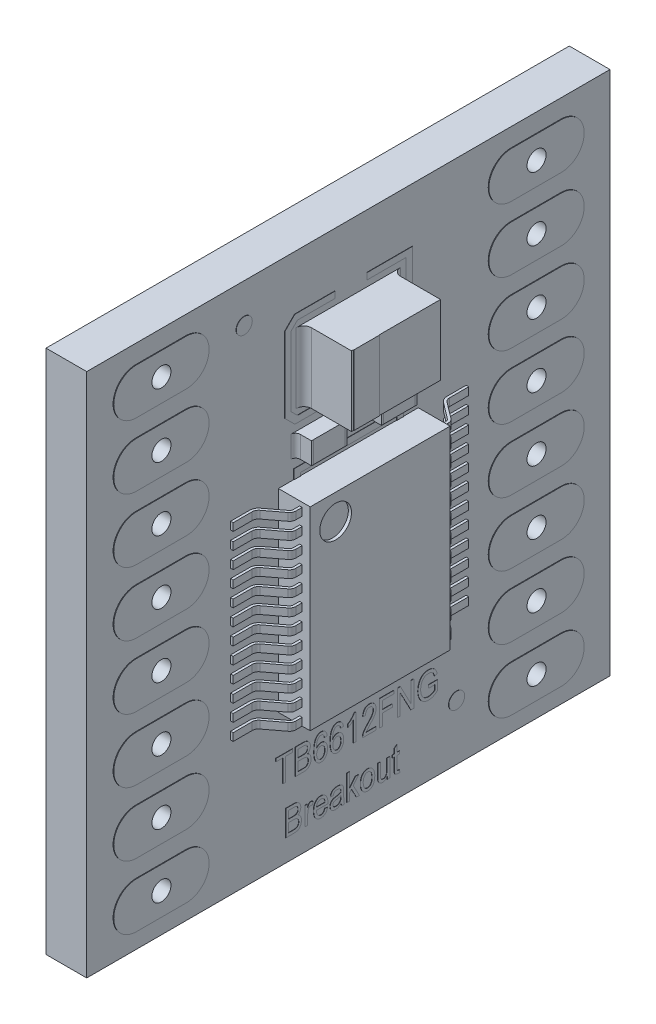
SolidWorks part; units mm, degrees
ref_plane "Front Plane" through (0, 0, 0) normal (0, 0, 1) x (1, 0, 0)
ref_plane "Top Plane" through (0, 0, 0) normal (0, 1, 0) x (1, 0, 0)
ref_plane "Right Plane" through (0, 0, 0) normal (1, 0, 0) x (0, 0, -1)
sketch "Sketch1" plane through (0, 0, 0) normal (1, 0, 0) x (0, 0, -1)
  line L1 (-10.4521, 10.4902) -> (10.4521, 10.4902)
  line L2 (-10.4521, 10.4902) -> (-10.4521, -10.4902)
  line L3 (-10.4521, -10.4902) -> (10.4521, -10.4902)
  line L4 (10.4521, 10.4902) -> (10.4521, -10.4902)
  line L5 (-10.4521, 10.4902) -> (10.4521, -10.4902) construction
  line L6 (-10.4521, -10.4902) -> (10.4521, 10.4902) construction
  point P0 (0, 0)
  dimension "D1" = 20.9804
  dimension "D2" = 20.9042
extrude "Boss-Extrude1" add sketch "Sketch1" along normal blind 1.6256
sketch "Sketch2" plane through (1.6256, 0, 0) normal (1, 0, 0) x (0, 0, -1)
  line L0 (-10.4521, -10.4902) -> (10.4521, -10.4902) construction
  line L1 (-2.794, 2.6162) -> (2.794, 2.6162)
  line L2 (-2.794, 2.6162) -> (-2.794, -5.1308)
  line L3 (-2.794, -5.1308) -> (2.794, -5.1308)
  line L4 (2.794, 2.6162) -> (2.794, -5.1308)
  line L5 (-2.794, 2.6162) -> (2.794, -5.1308) construction
  line L6 (-2.794, -5.1308) -> (2.794, 2.6162) construction
  point P0 (0, 0)
  dimension "D1" = 5.588
  dimension "D2" = 7.747
  dimension "D3" = 5.3594
extrude "Boss-Extrude2" add sketch "Sketch2" along normal blind 1.27
sketch "Sketch7" plane through (2.8956, 0, 0) normal (1, 0, 0) x (0, 0, -1)
  line L0 (-2.794, 2.6162) -> (-2.794, -5.1308) construction
  line L1 (2.794, 2.6162) -> (-2.794, 2.6162) construction
  circle A0 centre (-1.778, 1.6002) radius 0.635
  dimension "D1" = 1.27
  dimension "D2" = 1.016
  dimension "D3" = 1.016
extrude "Cut-Extrude2" cut sketch "Sketch7" against normal blind 0.127
sketch "Sketch4" plane through (1.6256, 0, 0) normal (1, 0, 0) x (0, 0, -1)
  line L0 (-7.493, 8.8392) -> (0, 8.8392) construction
  line L1 (0, 8.8392) -> (7.493, 8.8392) construction
  line L2 (0, 0) -> (0, 8.8392) construction
  line L3 (10.4521, 10.4902) -> (-10.4521, 10.4902) construction
  circle A0 centre (-7.493, 8.8392) radius 0.381
  circle A1 centre (7.493, 8.8392) radius 0.381
  dimension "D2" = 0.762
  dimension "D1" = 14.986
  dimension "D3" = 1.27
extrude "Cut-Extrude1" cut sketch "Sketch4" against normal through all
sketch "Sketch5" plane through (1.6256, 0, 0) normal (1, 0, 0) x (0, 0, -1)
  line L0 (-8.4836, 8.8392) -> (-6.5024, 8.8392) construction
  line L1 (-8.4836, 9.7536) -> (-6.5024, 9.7536)
  line L2 (-8.4836, 7.9248) -> (-6.5024, 7.9248)
  line L3 (6.5024, 8.8392) -> (8.4836, 8.8392) construction
  line L4 (6.5024, 9.7536) -> (8.4836, 9.7536)
  line L5 (6.5024, 7.9248) -> (8.4836, 7.9248)
  arc A0 (-8.4836, 9.7536) -> (-8.4836, 7.9248) centre (-8.4836, 8.8392) ccw
  arc A1 (-6.5024, 7.9248) -> (-6.5024, 9.7536) centre (-6.5024, 8.8392) ccw
  arc A2 (6.5024, 9.7536) -> (6.5024, 7.9248) centre (6.5024, 8.8392) ccw
  arc A3 (8.4836, 7.9248) -> (8.4836, 9.7536) centre (8.4836, 8.8392) ccw
  circle A6 centre (7.493, 8.8392) radius 0.381 construction
  circle A7 centre (-7.493, 8.8392) radius 0.381 construction
  circle A8 centre (7.493, 8.8392) radius 0.381
  circle A9 centre (-7.493, 8.8392) radius 0.381
  point P3 (-7.493, 8.8392)
  point P8 (7.493, 8.8392)
  point P18 (7.493, 8.8392)
  dimension "D2" = 3.81
  dimension "D1" = 1.8288
extrude "Boss-Extrude3" add sketch "Sketch5" along normal blind 0.0254
sketch "Sketch6" plane through (0, 0, 0) normal (-1, 0, 0) x (0, 0, 1)
  line L0 (-6.5024, 7.9248) -> (-8.4836, 7.9248) construction
  line L1 (-8.4836, 9.7536) -> (-6.5024, 9.7536) construction
  line L2 (8.4836, 7.9248) -> (6.5024, 7.9248) construction
  line L3 (6.5024, 9.7536) -> (8.4836, 9.7536) construction
  line L4 (-6.5024, 7.9248) -> (-8.4836, 7.9248)
  line L5 (-8.4836, 9.7536) -> (-6.5024, 9.7536)
  line L6 (8.4836, 7.9248) -> (6.5024, 7.9248)
  line L7 (6.5024, 9.7536) -> (8.4836, 9.7536)
  circle A0 centre (-7.493, 8.8392) radius 0.381 construction
  arc A1 (-6.5024, 7.9248) -> (-6.5024, 9.7536) centre (-6.5024, 8.8392) ccw construction
  arc A2 (-8.4836, 9.7536) -> (-8.4836, 7.9248) centre (-8.4836, 8.8392) ccw construction
  circle A3 centre (7.493, 8.8392) radius 0.381 construction
  arc A4 (6.5024, 9.7536) -> (6.5024, 7.9248) centre (6.5024, 8.8392) ccw construction
  arc A5 (8.4836, 7.9248) -> (8.4836, 9.7536) centre (8.4836, 8.8392) ccw construction
  circle A6 centre (-7.493, 8.8392) radius 0.381
  arc A7 (-6.5024, 7.9248) -> (-6.5024, 9.7536) centre (-6.5024, 8.8392) ccw
  arc A8 (-8.4836, 9.7536) -> (-8.4836, 7.9248) centre (-8.4836, 8.8392) ccw
  circle A9 centre (7.493, 8.8392) radius 0.381
  arc A10 (6.5024, 9.7536) -> (6.5024, 7.9248) centre (6.5024, 8.8392) ccw
  arc A11 (8.4836, 7.9248) -> (8.4836, 9.7536) centre (8.4836, 8.8392) ccw
extrude "Boss-Extrude4" add sketch "Sketch6" along normal blind 0.0254
pattern_linear "LPattern1" count 8 spacing 2.54 along (0, -1, 0) of "Cut-Extrude1", "Boss-Extrude3", "Boss-Extrude4"
sketch "Sketch11" plane through (1.6256, 0, 0) normal (1, 0, 0) x (0, 0, -1)
  circle A0 centre (-4.1683, 8.9453) radius 0.3175
  circle A1 centre (4.3185, -8.2635) radius 0.3175
  dimension "D1" = 0.635
extrude "Boss-Extrude8" add sketch "Sketch11" along normal blind 0.0127
sketch "Sketch9" plane through (1.6256, 0, 0) normal (1, 0, 0) x (0, 0, -1)
  line L0 (-1.397, 3.81) -> (0, 3.81) construction
  line L1 (-2.032, 4.2418) -> (-0.762, 4.2418)
  line L2 (-2.032, 4.2418) -> (-2.032, 3.3782)
  line L3 (-2.032, 3.3782) -> (-0.762, 3.3782)
  line L4 (-0.762, 4.2418) -> (-0.762, 3.3782)
  line L5 (-2.032, 4.2418) -> (-0.762, 3.3782) construction
  line L6 (-2.032, 3.3782) -> (-0.762, 4.2418) construction
  line L7 (0.762, 4.2418) -> (2.032, 4.2418)
  line L8 (0.762, 4.2418) -> (0.762, 3.3782)
  line L9 (0.762, 3.3782) -> (2.032, 3.3782)
  line L10 (2.032, 4.2418) -> (2.032, 3.3782)
  line L11 (0.762, 4.2418) -> (2.032, 3.3782) construction
  line L12 (0.762, 3.3782) -> (2.032, 4.2418) construction
  line L13 (0, 3.81) -> (1.397, 3.81) construction
  line L14 (0, 3.81) -> (0, 0) construction
  line L15 (2.794, 2.6162) -> (-2.794, 2.6162) construction
  point P0 (-1.397, 3.81)
  point P5 (1.397, 3.81)
  dimension "D1" = 0.8636
  dimension "D2" = 1.27
  dimension "D3" = 1.397
  dimension "D4" = 0.762
extrude "Boss-Extrude6" add sketch "Sketch9" along normal blind 0.635
sketch "Sketch10" plane through (1.6256, 0, 0) normal (1, 0, 0) x (0, 0, -1)
  line L1 (-0.762, 4.2418) -> (-0.6858, 4.2418)
  line L2 (-0.762, 4.2418) -> (-0.762, 3.3782)
  line L3 (-0.762, 3.3782) -> (-0.6858, 3.3782)
  line L4 (-0.6858, 4.2418) -> (-0.6858, 3.3782)
  line L5 (-2.032, 4.2418) -> (-2.1082, 4.2418)
  line L6 (-2.032, 4.2418) -> (-2.032, 3.3782)
  line L7 (-2.032, 3.3782) -> (-2.1082, 3.3782)
  line L8 (-2.1082, 4.2418) -> (-2.1082, 3.3782)
  line L9 (0.762, 4.2418) -> (0.6858, 4.2418)
  line L10 (0.762, 4.2418) -> (0.762, 3.3782)
  line L11 (0.762, 3.3782) -> (0.6858, 3.3782)
  line L12 (0.6858, 4.2418) -> (0.6858, 3.3782)
  line L13 (2.032, 4.2418) -> (2.1082, 4.2418)
  line L14 (2.032, 4.2418) -> (2.032, 3.3782)
  line L15 (2.032, 3.3782) -> (2.1082, 3.3782)
  line L16 (2.1082, 4.2418) -> (2.1082, 3.3782)
  line L17 (-2.032, 3.3782) -> (-0.762, 3.3782) construction
  dimension "D1" = 0.0762
extrude "Boss-Extrude7" add sketch "Sketch10" along normal blind 0.6363
fillet "Fillet1" radius 0.1905 4 edges at (1.6256, 3.81, -2.1082) (1.6256, 3.81, -0.6858) (1.6256, 3.81, 0.6858) (1.6256, 3.81, 2.1082)
sketch "Sketch12" plane through (1.6256, 0, 0) normal (1, 0, 0) x (0, 0, -1)
  line L0 (0, 0) -> (0, 6.4262) construction
  line L1 (-1.778, 5.0292) -> (1.778, 5.0292)
  line L2 (-1.778, 5.0292) -> (-1.778, 7.8232)
  line L3 (-1.778, 7.8232) -> (1.778, 7.8232)
  line L4 (1.778, 5.0292) -> (1.778, 7.8232)
  line L5 (-1.778, 5.0292) -> (1.778, 7.8232) construction
  line L6 (-1.778, 7.8232) -> (1.778, 5.0292) construction
  line L8 (10.4521, 10.4902) -> (-10.4521, 10.4902) construction
  point P0 (0, 6.4262)
  dimension "D1" = 2.794
  dimension "D2" = 3.556
  dimension "D3" = 2.667
extrude "Boss-Extrude9" add sketch "Sketch12" along normal blind 1.905
fillet "Fillet2" radius 0.3048 2 edges at (1.6256, 6.4262, -1.778) (1.6256, 6.4262, 1.778)
sketch "Sketch13" plane through (3.5306, 0, 0) normal (1, 0, 0) x (0, 0, -1)
  line L0 (1.778, 7.8232) -> (-1.778, 7.8232) construction
  line L1 (-1.6958, 7.8232) -> (-0.6798, 7.8232)
  line L2 (-1.6958, 7.8232) -> (-1.6958, 5.0292)
  line L3 (-1.6958, 5.0292) -> (-0.6798, 5.0292)
  line L4 (-0.6798, 7.8232) -> (-0.6798, 5.0292)
  line L5 (-2.0828, 5.0292) -> (2.0828, 5.0292) construction
  dimension "D1" = 1.016
extrude "Boss-Extrude10" add sketch "Sketch13" along normal blind 0.0127
sketch "Sketch14" plane through (0, -5.1308, 0) normal (0, -1, 0) x (1, 0, 0)
  line L0 (2.5745, -2.794) -> (2.5745, -3.048)
  line L1 (2.8956, -2.794) -> (1.6256, -2.794) construction
  line L2 (2.4739, -3.2504) -> (1.8278, -3.74)
  line L3 (1.7272, -3.9425) -> (1.7272, -4.7045)
  line L4 (2.4729, -2.794) -> (2.4729, -3.048)
  line L5 (2.4126, -3.1695) -> (1.7664, -3.659)
  line L6 (1.6256, -3.9425) -> (1.6256, -4.7045)
  line L7 (2.5745, -2.794) -> (2.4729, -2.794)
  line L8 (1.7272, -4.7045) -> (1.6256, -4.7045)
  line L9 (1.6256, 10.4521) -> (1.6256, -10.4521) construction
  line L10 (2.8956, 0) -> (-1.1531, 0) construction
  line L11 (2.8956, 2.794) -> (2.8956, -2.794) construction
  line L12 (2.5745, 2.794) -> (2.4729, 2.794)
  line L13 (2.5745, 2.794) -> (2.5745, 3.048)
  line L14 (2.4729, 2.794) -> (2.4729, 3.048)
  line L15 (2.4739, 3.2504) -> (1.8278, 3.74)
  line L16 (2.4126, 3.1695) -> (1.7664, 3.659)
  line L17 (1.7272, 3.9425) -> (1.7272, 4.7045)
  line L18 (1.7272, 4.7045) -> (1.6256, 4.7045)
  line L19 (1.6256, 3.9425) -> (1.6256, 4.7045)
  arc A0 (1.8278, -3.74) -> (1.7272, -3.9425) centre (1.9812, -3.9425) ccw
  arc A1 (2.5745, -3.048) -> (2.4739, -3.2504) centre (2.3205, -3.048) cw
  arc A2 (2.4729, -3.048) -> (2.4126, -3.1695) centre (2.3205, -3.048) cw
  arc A3 (1.7664, -3.659) -> (1.6256, -3.9425) centre (1.9812, -3.9425) ccw
  arc A4 (2.4729, 3.048) -> (2.4126, 3.1695) centre (2.3205, 3.048) ccw
  arc A5 (2.5745, 3.048) -> (2.4739, 3.2504) centre (2.3205, 3.048) ccw
  arc A6 (1.7664, 3.659) -> (1.6256, 3.9425) centre (1.9812, 3.9425) cw
  arc A7 (1.8278, 3.74) -> (1.7272, 3.9425) centre (1.9812, 3.9425) cw
  dimension "D1" = 0.254
  dimension "D3" = 232.848
  dimension "D4" = 0.254
  dimension "D5" = 0.762
  dimension "D2" = 0.1016
extrude "Boss-Extrude11" add sketch "Sketch14" against normal blind 0.3048
pattern_linear "LPattern2" count 12 spacing 0.6604 along (0, 1, 0) of "Boss-Extrude11"
sketch "Sketch8" plane through (1.6256, 0, 0) normal (1, 0, 0) x (0, 0, -1)
  line L0 (-2.1843, 2.9972) -> (2.1843, 2.9972)
  line L1 (-1.9303, 2.7432) -> (1.9303, 2.7432)
  line L2 (-1.9303, 2.7432) -> (-1.9303, -5.2578)
  line L3 (-1.9303, -5.2578) -> (1.9303, -5.2578)
  line L4 (1.9303, 2.7432) -> (1.9303, -5.2578)
  line L5 (-1.9303, 2.7432) -> (1.9303, -5.2578) construction
  line L6 (-1.9303, -5.2578) -> (1.9303, 2.7432) construction
  line L7 (2.1843, 2.9972) -> (2.1843, -5.5118)
  line L8 (-2.1843, -5.5118) -> (2.1843, -5.5118)
  line L9 (-2.1843, 2.9972) -> (-2.1843, -5.5118)
  line L10 (2.794, 2.6162) -> (-2.794, 2.6162) construction
  line L11 (-0.5427, 8.3278) -> (-0.5427, 8.0738)
  line L12 (-2.794, -5.1308) -> (2.794, -5.1308) construction
  line L13 (2.5533, 8.3278) -> (2.5533, 4.5246)
  line L14 (-2.0453, 8.0738) -> (-0.5427, 8.0738)
  line L15 (-2.2993, 7.8198) -> (-2.2993, 5.0326)
  line L16 (-2.0453, 4.7786) -> (-0.5427, 4.7786)
  line L17 (2.2993, 8.0738) -> (2.2993, 4.7786)
  line L18 (-2.2993, 8.0738) -> (-2.2993, 4.7786) construction
  line L19 (-2.2993, 7.8198) -> (-2.0453, 8.0738)
  line L20 (-2.1505, 4.5246) -> (-0.5427, 4.5246)
  line L21 (-2.5533, 7.925) -> (-2.1505, 8.3278)
  line L22 (-2.1505, 8.3278) -> (-0.5427, 8.3278)
  line L23 (0.7387, 8.3278) -> (0.7387, 8.0738)
  line L24 (0.7387, 8.3278) -> (2.5533, 8.3278)
  line L25 (-2.5533, 8.3278) -> (2.5533, 8.3278) construction
  line L26 (0.7387, 8.0738) -> (2.2993, 8.0738)
  line L27 (-2.2993, 8.0738) -> (2.2993, 8.0738) construction
  line L28 (-2.2993, 5.0326) -> (-2.0453, 4.7786)
  line L29 (-2.5533, 4.9274) -> (-2.1505, 4.5246)
  line L30 (0.7387, 4.7786) -> (2.2993, 4.7786)
  line L31 (-2.2993, 4.7786) -> (2.2993, 4.7786) construction
  line L32 (0.7387, 4.5246) -> (2.5533, 4.5246)
  line L33 (-2.5533, 4.5246) -> (2.5533, 4.5246) construction
  line L34 (0.7387, 4.7786) -> (0.7387, 4.5246)
  line L35 (-0.5427, 4.7786) -> (-0.5427, 4.5246)
  line L36 (-2.5533, 8.3278) -> (-2.5533, 4.5246) construction
  line L37 (-2.5533, 7.925) -> (-2.5533, 4.9274)
  line L38 (-2.4789, 7.9994) -> (-2.2249, 8.2534) construction
  line L39 (-2.4789, 4.853) -> (-2.2249, 4.599) construction
  line L40 (-2.5533, 7.8198) -> (-2.5533, 5.0326) construction
  text T0 "TB6612FNG\r\n Breakout" font "@Adobe Heiti Std R" height 1.016
  point P1 (0, -1.2573)
  point P14 (0, 6.4262)
  dimension "D2" = 0.127
  dimension "D3" = 0.127
  dimension "D5" = 0.254
  dimension "D1" = 0.254
  dimension "D4" = 0.254
  dimension "D6" = 0.254
  dimension "D7" = 0.254
extrude "Boss-Extrude5" add sketch "Sketch8" along normal blind 0.0127
sketch "Sketch15" plane through (0, 0, 0) normal (-1, 0, 0) x (0, 0, 1)
  line L0 (5.2079, 12.1114) -> (5.2079, -12.5412) construction
  text T0 "PWMA" font "Century Gothic" height 1.016
  text T1 "AIN2" font "Century Gothic" height 1.016
  text T2 "AIN1" font "Century Gothic" height 1.016
  text T3 "STBY" font "Century Gothic" height 1.016
  text T4 "BIN1" font "Century Gothic" height 1.016
  text T5 "BIN2" font "Century Gothic" height 1.016
  text T6 "PWMB" font "Century Gothic" height 1.016
  text T7 "GND" font "Century Gothic" height 1.016
  text T8 "VM" font "Century Gothic" height 1.016
  text T9 "VCC" font "Century Gothic" height 1.016
  text T10 "GND" font "Century Gothic" height 1.016
  text T11 "A01" font "Century Gothic" height 1.016
  text T12 "A02" font "Century Gothic" height 1.016
  text T13 "B02" font "Century Gothic" height 1.016
  text T14 "B01" font "Century Gothic" height 1.016
  text T15 "GND" font "Century Gothic" height 1.016
extrude "Boss-Extrude12" add sketch "Sketch15" along normal blind 0.0254
